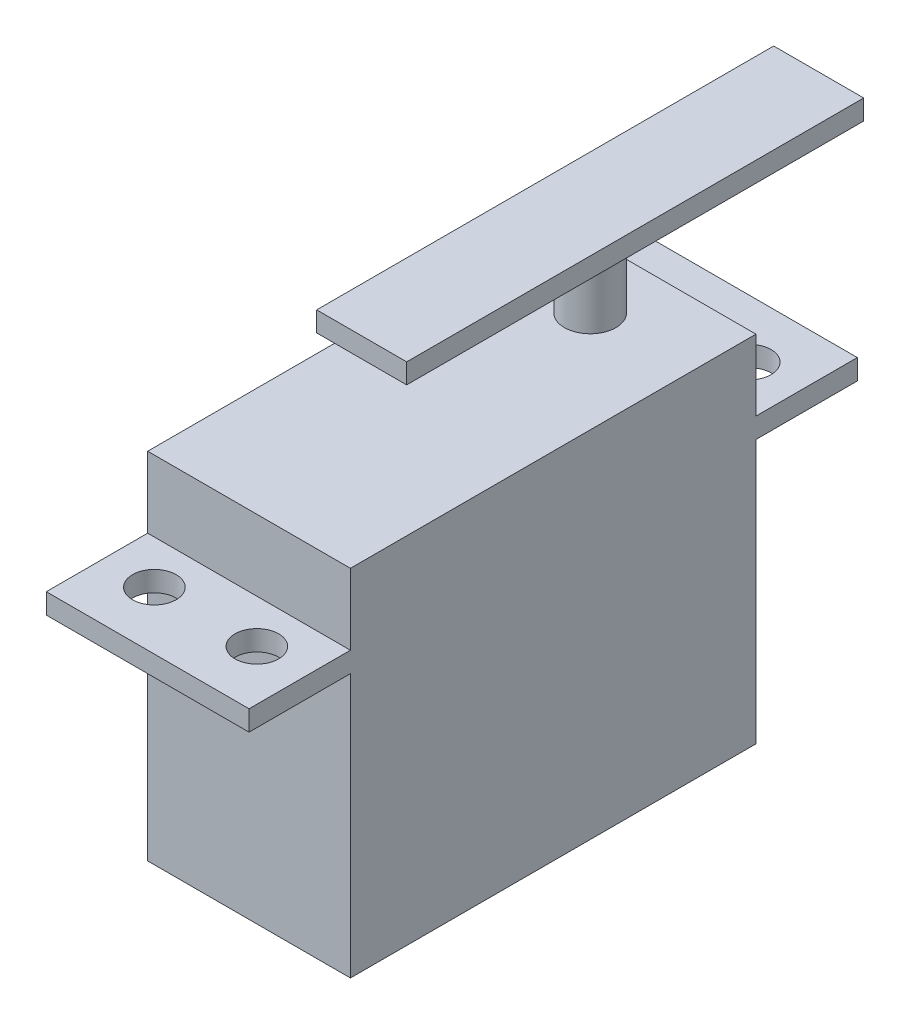
SolidWorks part; units mm, degrees
ref_plane "Front Plane" through (0, 0, 0) normal (0, 0, 1) x (1, 0, 0)
ref_plane "Top Plane" through (0, 0, 0) normal (0, 1, 0) x (1, 0, 0)
ref_plane "Right Plane" through (0, 0, 0) normal (1, 0, 0) x (0, 0, -1)
sketch "Sketch1" plane through (0, 0, 0) normal (0, 1, 0) x (1, 0, 0)
  line L1 (-10, 20) -> (10, 20)
  line L2 (-10, 20) -> (-10, -20)
  line L3 (-10, -20) -> (10, -20)
  line L4 (10, 20) -> (10, -20)
  line L5 (-10, 20) -> (10, -20) construction
  line L6 (-10, -20) -> (10, 20) construction
  point P0 (0, 0)
  dimension "D1" = 40
  dimension "D2" = 20
extrude "Boss-Extrude1" add sketch "Sketch1" against normal blind 26 and the other way blind 9
sketch "Sketch2" plane through (0, 9, 0) normal (0, 1, 0) x (1, 0, 0)
  line L0 (10, 20) -> (-10, 20) construction
  circle A0 centre (0, 13.65) radius 2.54
  dimension "D1" = 5.08
  dimension "D2" = 6.35
extrude "Boss-Extrude2" add sketch "Sketch2" along normal blind 7.33
sketch "Sketch3" plane through (0, 16.33, 0) normal (0, 1, 0) x (1, 0, 0)
  line L1 (-4.44, 36.19) -> (4.44, 36.19)
  line L2 (-4.44, 36.19) -> (-4.44, -8.89)
  line L3 (-4.44, -8.89) -> (4.44, -8.89)
  line L4 (4.44, 36.19) -> (4.44, -8.89)
  line L5 (-4.44, 36.19) -> (4.44, -8.89) construction
  line L6 (-4.44, -8.89) -> (4.44, 36.19) construction
  circle A0 centre (0, 13.65) radius 2.54 construction
  point P0 (0, 13.65)
  dimension "D1" = 8.88
  dimension "D2" = 45.08
extrude "Boss-Extrude3" add sketch "Sketch3" along normal blind 1.97
sketch "Sketch9" [suppressed] plane through (0, 16.33, 0) normal (0, 1, 0) x (1, 0, 0)
  line L1 (-22.54, 18.09) -> (22.54, 18.09)
  line L2 (-22.54, 18.09) -> (-22.54, 9.21)
  line L3 (-22.54, 9.21) -> (22.54, 9.21)
  line L4 (22.54, 18.09) -> (22.54, 9.21)
  line L5 (-22.54, 18.09) -> (22.54, 9.21) construction
  line L6 (-22.54, 9.21) -> (22.54, 18.09) construction
  point P0 (0, 13.65)
  dimension "D1" = 8.88
  dimension "D2" = 45.08
extrude "Boss-Extrude4" [suppressed] add sketch "Sketch9" along normal blind 1.97
sketch "Sketch6" plane through (0, 0, 0) normal (0, 1, 0) x (1, 0, 0)
  line L0 (10, -20) -> (-10, -20)
  line L1 (10, -20) -> (10, -30)
  line L2 (-10, -20) -> (-10, -30)
  line L3 (10, -30) -> (-10, -30)
  line L4 (10, -20) -> (10, 20) construction
  line L5 (-10, 20) -> (-10, -20) construction
  line L6 (-10, -20) -> (10, -20) construction
  line L7 (-24.365, 0) -> (24.365, 0) construction
  line L8 (-10, 20) -> (-10, 30)
  line L9 (10, 30) -> (-10, 30)
  line L10 (10, 20) -> (10, 30)
  line L11 (10, 20) -> (-10, 20)
  dimension "D1" = 10
extrude "Boss-Extrude5" add sketch "Sketch6" along normal blind 2
sketch "Sketch8" plane through (0, 0, 0) normal (0, 1, 0) x (1, 0, 0)
  line L1 (-5.055, 24.285) -> (5.055, 24.285) construction
  line L2 (-5.055, 24.285) -> (-5.055, -24.285) construction
  line L3 (-5.055, -24.285) -> (5.055, -24.285) construction
  line L4 (5.055, 24.285) -> (5.055, -24.285) construction
  line L5 (-5.055, 24.285) -> (5.055, -24.285) construction
  line L6 (-5.055, -24.285) -> (5.055, 24.285) construction
  circle A0 centre (5.055, -24.285) radius 2.15
  circle A1 centre (-5.055, -24.285) radius 2.15
  circle A2 centre (5.055, 24.285) radius 2.15
  circle A3 centre (-5.055, 24.285) radius 2.15
  point P0 (0, 0)
  dimension "D3" = 4.3
  dimension "D1" = 10.11
  dimension "D2" = 48.57
extrude "Cut-Extrude1" cut sketch "Sketch8" along normal blind 5.1594 contours A1 | A0 | A3 | A2
ref_axis "Axis1" through (0, 99.147, -13.65) along (0, -1, 0)
